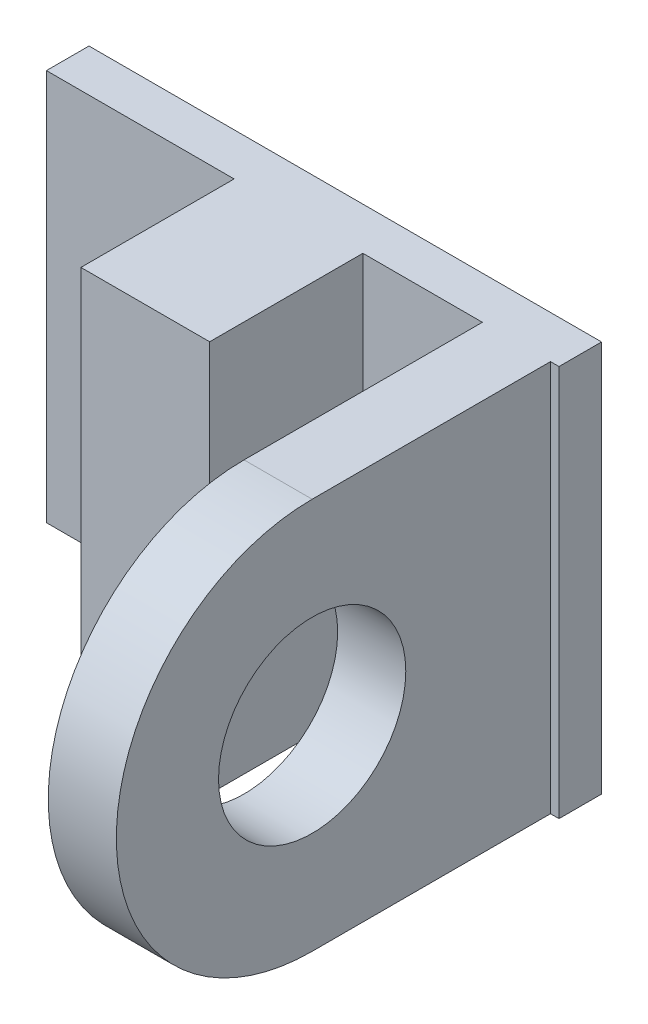
SolidWorks part; units mm, degrees
ref_plane "Plan de face" through (0, 0, 0) normal (0, 0, 1) x (1, 0, 0)
ref_plane "Plan de dessus" through (0, 0, 0) normal (0, 1, 0) x (1, 0, 0)
ref_plane "Plan de droite" through (0, 0, 0) normal (1, 0, 0) x (0, 0, -1)
sketch "Esquisse1" plane through (0, 0, 0) normal (0, 0, 1) x (1, 0, 0)
  line L0 (0, 0) -> (0, 83.4774) construction
  line L1 (0, 0) -> (132.8602, 0) construction
  line L3 (-46.214, -23) -> (14, -23)
  line L4 (-46.214, -23) -> (-46.214, 23)
  line L5 (-46.214, 23) -> (14, 23)
  line L6 (14, -23) -> (14, 23)
  dimension "D1" = 46
  dimension "D2" = 14
extrude "Boss.-Extru.1" add sketch "Esquisse1" along normal blind 5
sketch "Esquisse2" plane through (0, 0, 5) normal (0, 0, 1) x (1, 0, 0)
  line L0 (0, 0) -> (40.5234, 0) construction
  line L2 (0, 0) -> (0, 23) construction
  line L3 (14, 23) -> (-46.214, 23) construction
  line L5 (5, -23) -> (13, -23)
  line L6 (5, -23) -> (5, 23)
  line L7 (5, 23) -> (13, 23)
  line L8 (13, -23) -> (13, 23)
  line L9 (5, -23) -> (13, 23) construction
  line L10 (5, 23) -> (13, -23) construction
  line L11 (-24.1641, -23) -> (-9.0379, -23)
  line L12 (-24.1641, -23) -> (-24.1641, 23)
  line L13 (-24.1641, 23) -> (-9.0379, 23)
  line L14 (-9.0379, -23) -> (-9.0379, 23)
  line L15 (-24.1641, -23) -> (-9.0379, 23) construction
  line L16 (-24.1641, 23) -> (-9.0379, -23) construction
  point P1 (-16.601, 0)
  point P5 (9, 0)
  dimension "D1" = 8
  dimension "D2" = 5
extrude "Boss.-Extru.2" add sketch "Esquisse2" along normal blind 6
sketch "Esquisse8" plane through (5, 0, 0) normal (-1, 0, 0) x (0, 0, 1)
  line L0 (0, 0) -> (56, 0) construction
  line L1 (5, 23) -> (5, -23) construction
  line L2 (33, -23) -> (11, -23)
  line L4 (33, 23) -> (11, 23)
  line L5 (11, -23) -> (11, 23)
  line L6 (11, 23) -> (11, -23) construction
  circle A0 centre (33, 0) radius 11
  arc A2 (33, -23) -> (33, 23) centre (33, 0) ccw
  point P3 (43.9422, 0)
  dimension "D1" = 22
  dimension "D3" = 23
  dimension "D2" = 28
extrude "Boss.-Extru.4" add sketch "Esquisse8" against normal up to surface (8 mm away) up to face at (13, 0, 8)
sketch "Esquisse10" plane through (-24.1641, 0, 0) normal (-1, 0, 0) x (0, 0, 1)
  line L0 (0, 0) -> (33, 0) construction
  line L2 (11, 23) -> (23, 23)
  line L3 (11, 23) -> (11, -23)
  line L4 (11, -23) -> (23, -23)
  line L5 (23, 23) -> (23, -23)
  circle A0 centre (33, 0) radius 11 construction
  circle A1 centre (33, 0) radius 11 construction
  dimension "D1" = 10
extrude "Boss.-Extru.5" add sketch "Esquisse10" against normal up to surface (15.1262 mm away) contours L5 L4 L3 L2 up to face at (-9.0379, 0, 8)
ref_axis "Axe1" through (0, 0, -2.85) along (0, 0, 1)
